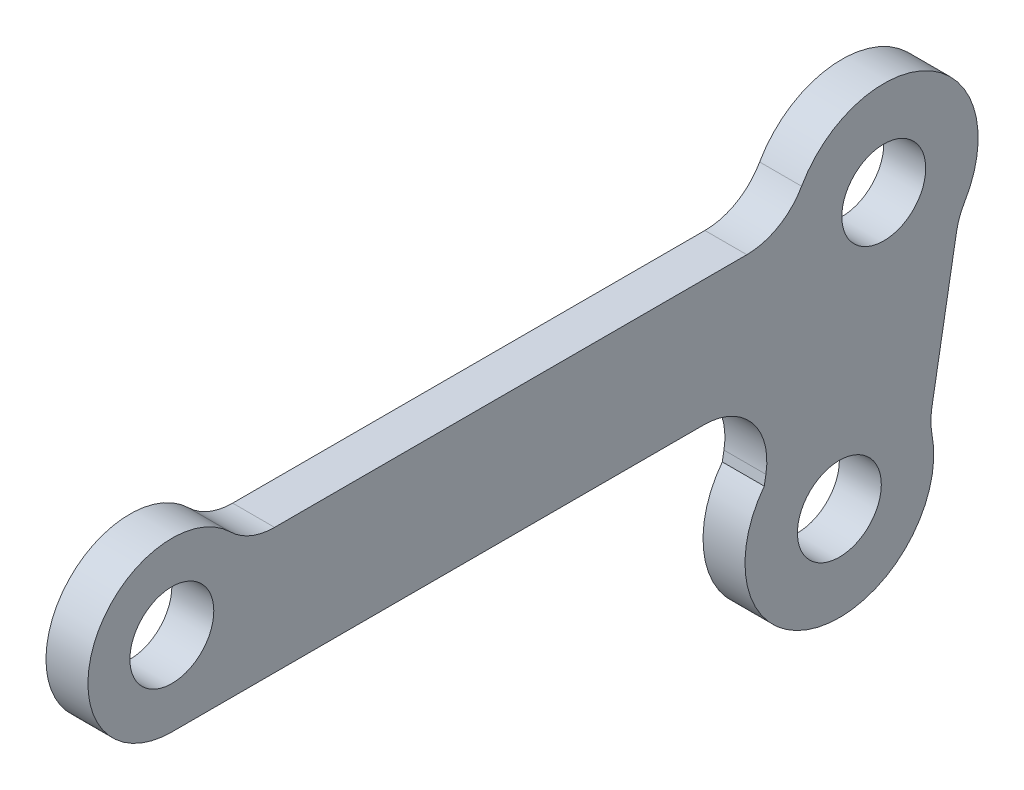
SolidWorks part; units mm, degrees
ref_plane "前视基准面" through (0, 0, 0) normal (0, 0, 1) x (1, 0, 0)
ref_plane "上视基准面" through (0, 0, 0) normal (0, 1, 0) x (1, 0, 0)
ref_plane "右视基准面" through (0, 0, 0) normal (1, 0, 0) x (0, 0, -1)
other "Configuration Table"
sketch "草图1" plane through (0, 0, 0) normal (1, 0, 0) x (0, 0, -1)
  line L1 (-30, 0) -> (0, 0)
  line L2 (-30, 0) -> (-30, -6)
  line L3 (-30, -6) -> (0, -6)
  line L4 (0, 0) -> (0, -6)
  line L5 (0, 0) -> (7.8785, -1.3892)
  line L6 (0, 0) -> (-2.1159, -12)
  line L7 (-2.1159, -12) -> (5.7625, -13.3892)
  line L8 (7.8785, -1.3892) -> (5.7625, -13.3892)
  circle A0 centre (-30, -2) radius 4
  circle A1 centre (3.9392, -0.6946) radius 4.5
  circle A2 centre (1.8233, -12.6946) radius 4.5
  circle A3 centre (-30, -2) radius 2
  circle A4 centre (3.9392, -0.6946) radius 2
  circle A5 centre (1.8233, -12.6946) radius 2
  dimension "D5" = 8
  dimension "D6" = 9
  dimension "D7" = 9
  dimension "D9" = 4
  dimension "D1" = 6
  dimension "D2" = 8
  dimension "D3" = 80
  dimension "D4" = 30
  dimension "D8" = 12
extrude "凸台-拉伸1" add sketch "草图1" along normal blind 2 contours A0 | L1 L4 L3 L2 | A1 | L5 L8 L7 L6 | A2
extrude "切除-拉伸1" cut sketch "草图1<3>" along normal through all contours A3 | A4 | A5
sketch "草图1<3>" plane through (0, 0, 0) normal (1, 0, 0) x (0, 0, -1) same geometry as "草图1"
fillet "圆角1" radius 3 5 edges at (1, -11.359, -6.1205) (1, -3.4194, -7.5205) (1, 0, 0.5068) (1, 0, 26.5359) (1, -6, 1.058)
